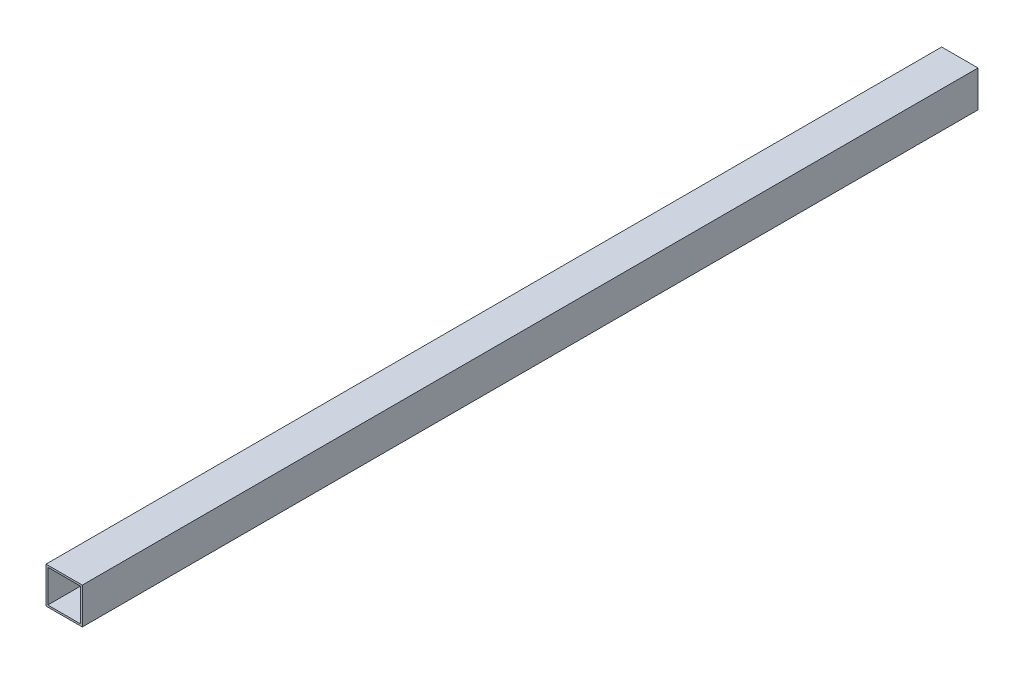
SolidWorks part; units mm, degrees
ref_plane "前视基准面" through (0, 0, 0) normal (0, 0, 1) x (1, 0, 0)
ref_plane "上视基准面" through (0, 0, 0) normal (0, 1, 0) x (1, 0, 0)
ref_plane "右视基准面" through (0, 0, 0) normal (1, 0, 0) x (0, 0, -1)
other "Configuration Table"
sketch "草图1" plane through (0, 0, 0) normal (0, 0, 1) x (1, 0, 0)
  line L0 (-9, 9) -> (-9, -9)
  line L1 (-10, 10) -> (10, 10)
  line L2 (-10, 10) -> (-10, -10)
  line L3 (-10, -10) -> (10, -10)
  line L4 (10, 10) -> (10, -10)
  line L5 (-10, 10) -> (10, -10) construction
  line L6 (-10, -10) -> (10, 10) construction
  line L7 (-9, -9) -> (9, -9)
  line L8 (9, 9) -> (9, -9)
  line L9 (-9, 9) -> (9, 9)
  point P0 (0, 0)
  dimension "D1" = 20
  dimension "D2" = 20
  dimension "D3" = 1
extrude "凸台-拉伸1" add sketch "草图1" along normal blind 493.33
